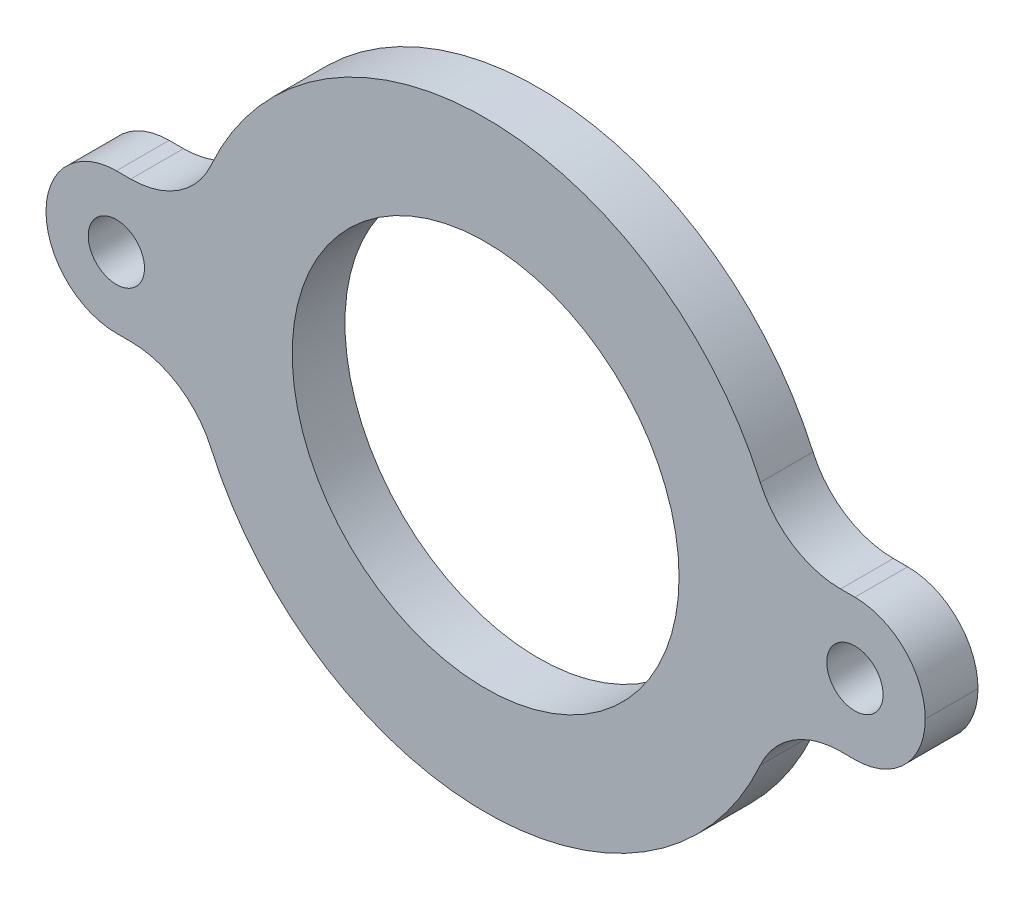
SolidWorks part; units mm, degrees
material "MDF"
ref_plane "Plano frontal" through (0, 0, 0) normal (0, 0, 1) x (1, 0, 0)
ref_plane "Plano superior" through (0, 0, 0) normal (0, 1, 0) x (1, 0, 0)
ref_plane "Plano direito" through (0, 0, 0) normal (1, 0, 0) x (0, 0, -1)
sketch "Esboço1" plane through (0, 0, 0) normal (0, 0, 1) x (1, 0, 0)
  line L0 (-19.5214, 0) -> (-12, 0) construction
  line L1 (-21, 0) -> (21, 0) construction
  line L2 (-25, 4) -> (-16.6256, 4)
  line L3 (0, 0) -> (0, 11) construction
  line L4 (25, 4) -> (16.6256, 4)
  line L5 (25, -4) -> (16.6256, -4)
  line L6 (-25, -4) -> (-16.6256, -4)
  line L7 (-25, -4) -> (-25, 4)
  line L8 (25, 4) -> (25, -4)
  circle A0 centre (0, 0) radius 11
  circle A1 centre (0, 0) radius 12 construction
  circle A3 centre (-21, 0) radius 1.6
  circle A4 centre (21, 0) radius 1.6
  arc A5 (-16.6256, 4) -> (16.6256, 4) centre (0, 0) cw
  arc A6 (-16.6256, -4) -> (16.6256, -4) centre (0, 0) ccw
  circle A7 centre (-13.5, 0) radius 3 construction
  point P5 (-12, 0)
  point P6 (-19.5214, 0)
  point P18 (0, 17.1)
  point P22 (0, 12)
  point P23 (0, 11)
  dimension "D1" = 22
  dimension "D2" = 24
  dimension "D3" = 3.2
  dimension "D7" = 17.1
  dimension "D4" = 6
  dimension "D8" = 27
  dimension "D5" = 4
  dimension "D6" = 4
  dimension "D9" = 7.5
extrude "Ressalto-extrusão1" add sketch "Esboço1" along normal blind 3
fillet "Filete2" radius 5 4 edges at (16.6256, 4, 1.5) (16.6256, -4, 1.5) (-16.6256, -4, 1.5) (-16.6256, 4, 1.5)
fillet "Filete3" radius 4 4 edges at (25, -4, 1.5) (25, 4, 1.5) (-25, -4, 1.5) (-25, 4, 1.5)
